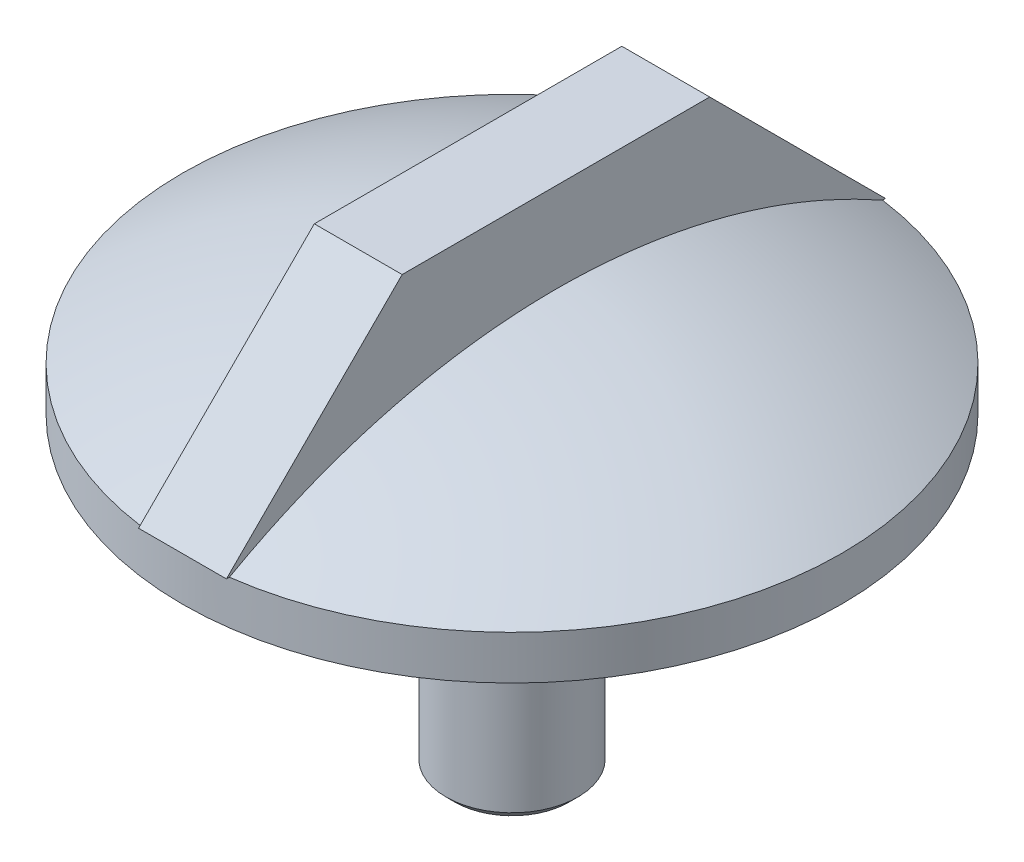
SolidWorks part; units mm, degrees
material "Copper"
ref_plane "Front Plane" through (0, 0, 0) normal (0, 0, 1) x (1, 0, 0)
ref_plane "Top Plane" through (0, 0, 0) normal (0, 1, 0) x (1, 0, 0)
ref_plane "Right Plane" through (0, 0, 0) normal (1, 0, 0) x (0, 0, -1)
sketch "Sketch1" plane through (0, 0, 0) normal (0, 1, 0) x (1, 0, 0)
  circle A0 centre (0, 0) radius 7.5
  dimension "D1" = 15
extrude "Boss-Extrude1" add sketch "Sketch1" along normal blind 1
sketch "Sketch3" plane through (0, 0, 0) normal (0, 0, 1) x (1, 0, 0)
  line L0 (0, 1) -> (0, 3)
  line L1 (7.5, 1) -> (-7.5, 1) construction
  line L2 (0, 1) -> (7.5, 1)
  spline S0 degree 2 poles (7.5, 1) (4.015, 2.9675) (0, 3) knots 0 0 0 1 1 1
revolve "Revolve1" add sketch "Sketch3" angle 360 about L0
sketch "Sketch4" plane through (0, 0, 0) normal (1, 0, 0) x (0, 0, -1)
  line L0 (-7.5, 1) -> (-3.5, 1)
  line L1 (-7.5, 1) -> (7.5, 1) construction
  line L3 (7.5, 1) -> (3.5, 1)
  line L5 (3.5, 5) -> (7.5, 1)
  line L6 (3.5, 5) -> (-3.5, 5)
  line L7 (-7.5, 1) -> (-3.5, 5)
  line L8 (3.5, 1) -> (-3.5, 1)
extrude "Boss-Extrude2" add sketch "Sketch4" along normal blind 1 and the other way blind 1
sketch "Sketch5" plane through (0, 0, 0) normal (0, -1, 0) x (1, 0, 0)
  circle A0 centre (0, 0) radius 1.5
extrude "Boss-Extrude3" add sketch "Sketch5" along normal blind 7
cosmetic thread "Cosmetic Thread1" parameters "D1"=7, "D2"=2
chamfer "Chamfer1" distance 0.2 angle 45 1 edges at (0, -7, -1.5)
